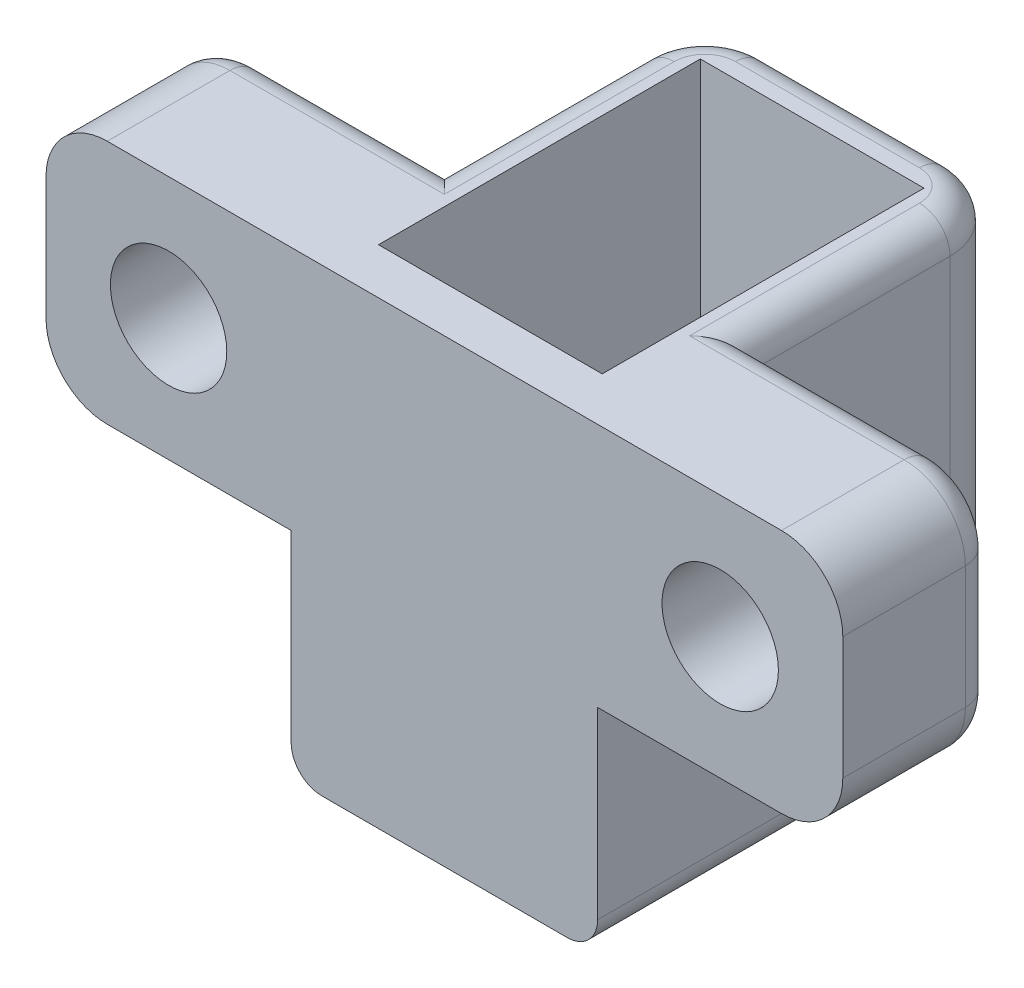
SolidWorks part; units mm, degrees
material "ABS"
ref_plane "Front Plane" through (0, 0, 0) normal (0, 0, 1) x (1, 0, 0)
ref_plane "Top Plane" through (0, 0, 0) normal (0, 1, 0) x (1, 0, 0)
ref_plane "Right Plane" through (0, 0, 0) normal (1, 0, 0) x (0, 0, -1)
sketch "Sketch1" plane through (0, 0, 0) normal (0, 1, 0) x (1, 0, 0)
  line L1 (-5, 6.75) -> (5, 6.75)
  line L2 (-5, 6.75) -> (-5, -6.75)
  line L3 (-5, -6.75) -> (5, -6.75)
  line L4 (5, 6.75) -> (5, -6.75)
  line L5 (-5, 6.75) -> (5, -6.75) construction
  line L6 (-5, -6.75) -> (5, 6.75) construction
  line L7 (-3.65, 5.25) -> (3.65, 5.25)
  line L8 (-3.65, 5.25) -> (-3.65, -5.25)
  line L9 (-3.65, -5.25) -> (3.65, -5.25)
  line L10 (3.65, 5.25) -> (3.65, -5.25)
  line L28 (-3.15, 5.25) -> (3.15, 5.25)
  line L29 (-3.15, 5.25) -> (-3.15, -5.25)
  line L30 (-3.15, -5.25) -> (3.15, -5.25)
  line L31 (3.15, 5.25) -> (3.15, -5.25)
  line L32 (-3.15, 5.25) -> (3.15, -5.25) construction
  line L33 (-3.15, -5.25) -> (3.15, 5.25) construction
  point P0 (0, 0)
  point P14 (3.65, 0)
  point P18 (0, 0)
  point P24 (0, 5.25)
  dimension "D1" = 10
  dimension "D2" = 13.5
  dimension "D3" = 10.5
  dimension "D4" = 7.3
  dimension "D6" = 6.3
  dimension "D7" = 10.5
extrude "Boss-Extrude1" add sketch "Sketch1" along normal blind 15 contours L4 L1 L2 L3 L7 L10 L9 L8 region at (0, 0, -6.582)
extrude "Boss-Extrude2" add sketch "Sketch1<3>" along normal blind 6.5 contours L29 L7 L8 L9 | L7 L31 L9 L10 region at (-3.4, 0, 0) region at (3.4, 0, 0)
sketch "Sketch1<3>" plane through (0, 0, 0) normal (0, 1, 0) x (1, 0, 0) same geometry as "Sketch1"
sketch "Sketch2" plane through (0, 0, 6.75) normal (0, 0, 1) x (1, 0, 0)
  line L0 (-5, 7) -> (-11, 7)
  line L3 (-13, 9) -> (-13, 13)
  line L4 (-5, 15) -> (-5, 0) construction
  line L5 (-11, 15) -> (-5, 15)
  line L6 (-5, 15) -> (-5, 7)
  line L7 (0, -55) -> (0, 55) construction
  line L8 (11, 15) -> (5, 15)
  line L9 (13, 9) -> (13, 13)
  line L10 (5, 7) -> (11, 7)
  line L11 (5, 15) -> (5, 7)
  line L12 (-5, 15) -> (5, 15) construction
  arc A2 (-11, 7) -> (-13, 9) centre (-11, 9) cw
  arc A3 (-13, 13) -> (-11, 15) centre (-11, 13) cw
  arc A4 (13, 13) -> (11, 15) centre (11, 13) ccw
  arc A5 (11, 7) -> (13, 9) centre (11, 9) ccw
  point P6 (-13, 7)
  point P13 (-13, 15)
  line M7 (5, 0) -> (5, 15)
  dimension "D4" = 2
  dimension "D1" = 8
  dimension "D3" = 8
extrude "Boss-Extrude3" add sketch "Sketch2" against normal blind 5 contours L10 A5 L9 A4 L8 M7 | L3 A3 L5 L6 L0 A2 region at (8.9021, 11, 6.75)
hole_wizard "#6 Clearance Hole1" positions "Sketch3" profile "Sketch4" hole size "#6" standard "ANSI Inch" end condition through all
sketch "Sketch3" plane through (0, 0, 6.75) normal (0, 0, 1) x (1, 0, 0)
  line L1 (-13, 9) -> (-13, 13) construction
  line L2 (13, 9) -> (13, 13) construction
  point P0 (-9, 11)
  point P2 (9, 11)
  point P9 (-13, 11)
  point P13 (13, 11)
  dimension "D1" = 4
  dimension "D2" = 4
sketch "Sketch4" plane through (-9, 11, 6.75) normal (1, 0, 0) x (0, -1, 0)
  line L0 (0, 0) -> (0, 13.5)
  line L1 (0, 13.5) -> (1.8986, 13.5)
  line L2 (1.8986, 13.5) -> (1.8986, 0)
  line L5 (1.8986, 0) -> (0, 0)
  line L11 (0, -6.35) -> (0, 107.95) construction
  dimension "Thru Hole Dia." = 3.7973
  dimension "Thru Hole Depth" = 13.5
sketch "Sketch5" plane through (0, 0, 0) normal (0, -1, 0) x (1, 0, 0)
  line L1 (-3.15, 5.25) -> (3.15, 5.25)
  line L2 (-3.15, 5.25) -> (-3.15, -5.25)
  line L3 (-3.15, -5.25) -> (3.15, -5.25)
  line L4 (3.15, 5.25) -> (3.15, -5.25)
  line L5 (-3.15, 5.25) -> (3.15, -5.25) construction
  line L6 (-3.15, -5.25) -> (3.15, 5.25) construction
  line L7 (-3.15, 5.25) -> (3.15, 5.25) construction
  line L9 (-2.15, 4.25) -> (2.15, 4.25)
  line L10 (-2.15, 4.25) -> (-2.15, -4.25)
  line L11 (-2.15, -4.25) -> (2.15, -4.25)
  line L12 (2.15, 4.25) -> (2.15, -4.25)
  line L13 (-2.15, 4.25) -> (2.15, -4.25) construction
  line L14 (-2.15, -4.25) -> (2.15, 4.25) construction
  line L23 (3.15, -5.25) -> (3.15, 5.25) construction
  point P0 (0, 0)
  point P13 (0, 0)
  dimension "D1" = 1
  dimension "D2" = 1
  dimension "D3" = 3.15
extrude "Boss-Extrude4" add sketch "Sketch5" against normal blind 1.5
fillet "Fillet1" radius 2 2 edges at (5, 7.5, -6.75) (-5, 7.5, -6.75)
fillet "Fillet2" radius 1 4 edges at (-2.15, 1.5, 0) (0, 1.5, 4.25) (0, 1.5, -4.25) (2.15, 1.5, 0) profile chamfer
fillet "Fillet3" radius 1 20 edges at (-5, 15, -1.5) (-4.4142, 15, -6.1642) (0, 15, -6.75) (4.4142, 15, -6.1642) (5, 15, -1.5) (-8, 7, 1.75) (-12.4142, 7.5858, 1.75) (-13, 11, 1.75) (-12.4142, 14.4142, 1.75) (8, 7, 1.75) (12.4142, 7.5858, 1.75) (13, 11, 1.75) (12.4142, 14.4142, 1.75) (-8, 15, 1.75) (8, 15, 1.75) (-5, 0, 1) (-4.4142, 0, -6.1642) (0, 0, -6.75) (4.4142, 0, -6.1642) (5, 0, 1)
equation "\"D1@Boss-Extrude2\"=15-8.5"
equation "\"D7@Sketch1\"=\"D3@Sketch1\""
equation "\"D3@Sketch5\"=6.3/2"
